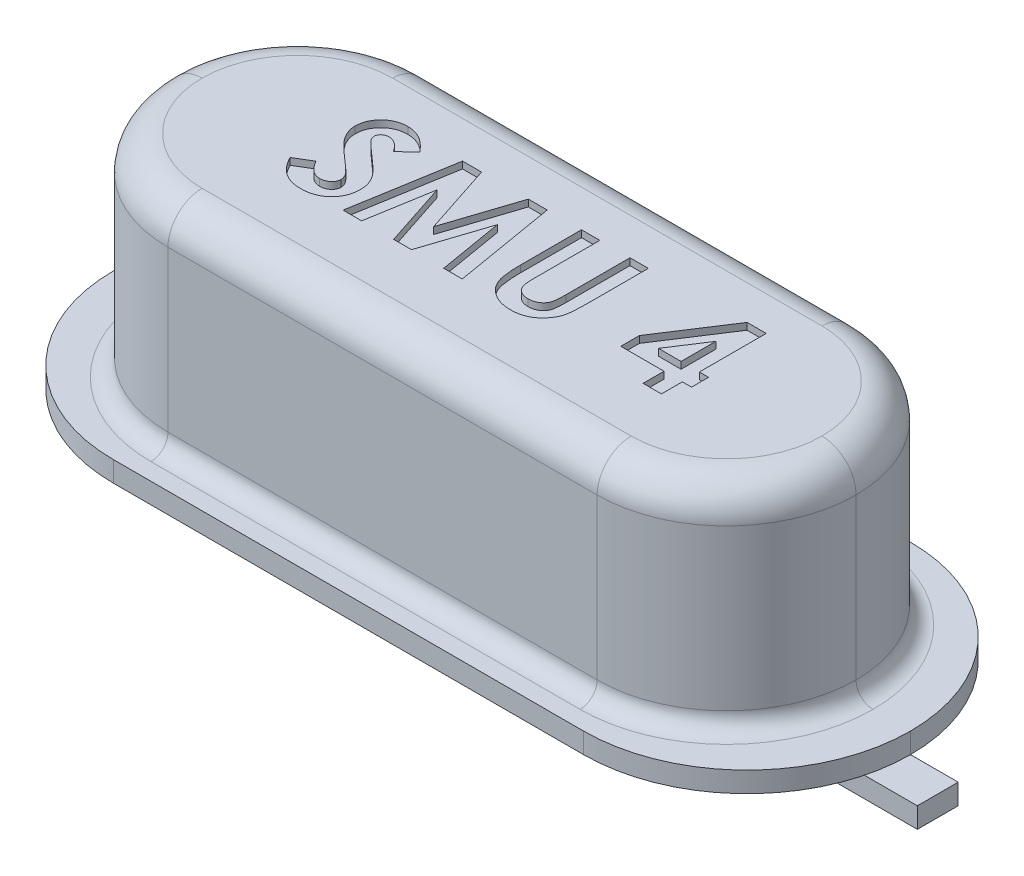
SolidWorks part; units mm, degrees
ref_plane "Plano frontal" through (0, 0, 0) normal (0, 0, 1) x (1, 0, 0)
ref_plane "Plano superior" through (0, 0, 0) normal (0, 1, 0) x (1, 0, 0)
ref_plane "Plano direito" through (0, 0, 0) normal (1, 0, 0) x (0, 0, -1)
sketch "Esboço1" plane through (0, 0, 0) normal (0, 1, 0) x (1, 0, 0)
  line L0 (-5.85, 2.4) -> (5.85, -2.4) construction
  line L1 (-5.85, 2.4) -> (5.85, 2.4)
  line L2 (-5.85, 2.4) -> (-5.85, -2.4)
  line L3 (-5.85, -2.4) -> (5.85, -2.4)
  line L4 (5.85, 2.4) -> (5.85, -2.4)
  dimension "D1" = 11.7
  dimension "D2" = 4.8
extrude "Extrusão1" add sketch "Esboço1" along normal blind 0.3
fillet "Filete1" radius 2.4 4 edges at (-5.85, 0.15, 2.4) (-5.85, 0.15, -2.4) (5.85, 0.15, -2.4) (5.85, 0.15, 2.4)
sketch "Esboço7" plane through (0, 0, 0) normal (0, -1, 0) x (1, 0, 0)
  line L0 (-5.85, 0) -> (5.85, 0) construction
  line L1 (-2.55, -0.3) -> (-2.55, 0.3) construction
  line L2 (-2.7, 0.3) -> (-2.4, 0.3)
  line L3 (-2.7, 0.3) -> (-2.7, -0.3)
  line L4 (-2.7, -0.3) -> (-2.4, -0.3)
  line L5 (-2.4, 0.3) -> (-2.4, -0.3)
  line L6 (2.4, 0.3) -> (2.7, 0.3)
  line L7 (2.4, 0.3) -> (2.4, -0.3)
  line L8 (2.4, -0.3) -> (2.7, -0.3)
  line L9 (2.7, 0.3) -> (2.7, -0.3)
  line L10 (2.55, -0.3) -> (2.55, 0.3) construction
  point P12 (-2.4, 0)
  point P13 (2.7, 0)
  dimension "D1" = 0.3
  dimension "D2" = 0.3
  dimension "D3" = 0.6
  dimension "D4" = 0.6
  dimension "D5" = 3.3
  dimension "D6" = 3.3
extrude "Extrusão2" add sketch "Esboço7" along normal blind 0.6
sketch "Esboço8" plane through (-2.7, 0, 0) normal (-1, 0, 0) x (0, 0, 1)
  line L0 (0.3, -0.6) -> (-0.3, -0.6) construction
  line L1 (-0.3, -0.3) -> (0.3, -0.3)
  line L2 (-0.3, -0.3) -> (-0.3, -0.6)
  line L3 (-0.3, -0.6) -> (0.3, -0.6)
  line L4 (0.3, -0.3) -> (0.3, -0.6)
  line L5 (-0.3, -0.6) -> (-0.3, 0) construction
  line L6 (0.3, -0.6) -> (0.3, 0) construction
  dimension "D1" = 0.3
extrude "Extrusão3" add sketch "Esboço8" along normal blind 3.55
sketch "Esboço9" plane through (2.7, 0, 0) normal (1, 0, 0) x (0, 0, -1)
  line L0 (0.3, -0.6) -> (-0.3, -0.6) construction
  line L1 (-0.3, -0.3) -> (0.3, -0.3)
  line L2 (-0.3, -0.3) -> (-0.3, -0.6)
  line L3 (-0.3, -0.6) -> (0.3, -0.6)
  line L4 (0.3, -0.3) -> (0.3, -0.6)
  line L5 (-0.3, -0.6) -> (-0.3, 0) construction
  line L6 (0.3, -0.6) -> (0.3, 0) construction
  dimension "D1" = 0.3
extrude "Extrusão4" add sketch "Esboço9" along normal blind 3.55
fillet "Filete2" radius 0.3 2 edges at (-2.4, -0.6, 0) (2.4, -0.6, 0)
sketch "Esboço11" plane through (0, 0.3, 0) normal (0, 1, 0) x (1, 0, 0)
  line L0 (-5.85, 0) -> (5.85, 0) construction
  line L2 (-5.05, 1.9) -> (5.05, 1.9)
  line L3 (-5.05, 1.9) -> (-5.05, -1.9)
  line L4 (-5.05, -1.9) -> (5.05, -1.9)
  line L5 (5.05, 1.9) -> (5.05, -1.9)
  point P8 (5.05, 0)
  point P9 (0, 1.9)
  dimension "D1" = 10.1
  dimension "D2" = 3.8
extrude "Extrusão5" add sketch "Esboço11" along normal blind 3.1
fillet "Filete3" radius 1.9 4 edges at (-5.05, 1.85, -1.9) (-5.05, 1.85, 1.9) (5.05, 1.85, 1.9) (5.05, 1.85, -1.9)
fillet "Filete4" radius 0.25 6 edges at (-4.4935, 0.3, 1.3435) (-4.4935, 0.3, -1.3435) (0, 0.3, -1.9) (4.4935, 0.3, -1.3435) (4.4935, 0.3, 1.3435) (0, 0.3, 1.9)
fillet "Filete5" radius 0.5 6 edges at (4.4935, 3.4, -1.3435) (4.4935, 3.4, 1.3435) (0, 3.4, 1.9) (-4.4935, 3.4, 1.3435) (-4.4935, 3.4, -1.3435) (0, 3.4, -1.9)
sketch "Esboço12" plane through (0, 3.4, 0) normal (0, 1, 0) x (1, 0, 0)
  text T0 "SMU 4" font "Century Gothic" height 1.5
extrude "Extrusão6" cut sketch "Esboço12" against normal blind 0.1
